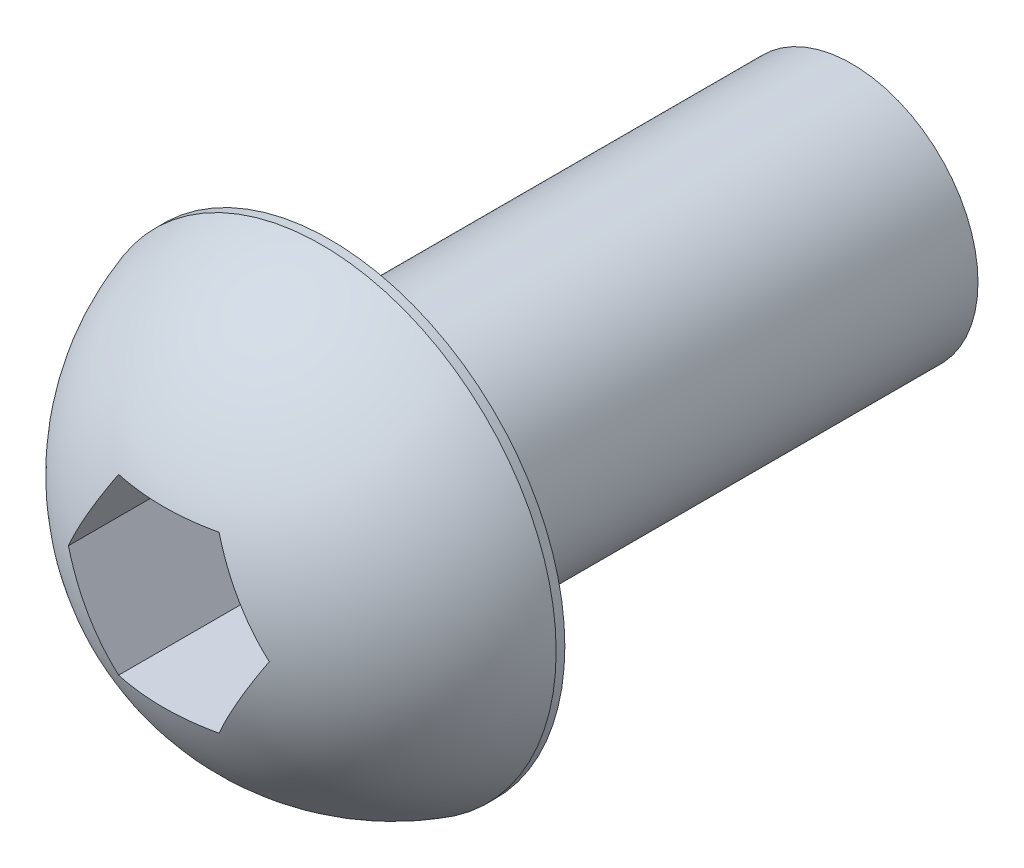
SolidWorks part; units mm, degrees
ref_plane "Front" through (0, 0, 0) normal (0, 0, 1) x (1, 0, 0)
ref_plane "Top" through (0, 0, 0) normal (0, 1, 0) x (1, 0, 0)
ref_plane "Right" through (0, 0, 0) normal (1, 0, 0) x (0, 0, -1)
sketch "Sketch1" plane through (0, 0, 0) normal (0, 0, 1) x (1, 0, 0)
  circle A0 centre (0, 0) radius 1.45
  dimension "D1" = 2.9
extrude "Boss-Extrude1" add sketch "Sketch1" along normal blind 6
cosmetic thread "Cosmetic Thread1" parameters "D2"=1.993
sketch "Sketch2" plane through (0, 0, 6) normal (0, 0, 1) x (1, 0, 0)
  circle A0 centre (0, 0) radius 2.7
  dimension "D1" = 5.4
extrude "Boss-Extrude2" add sketch "Sketch2" along normal blind 0.1
dome "Dome1" faces to dome 1 distance 2 reverse direction no elliptical dome no face at (2.7, 0, 6.1) parameters "D1"=2
sketch "Sketch3" plane through (0, 0, 6) normal (0, 0, -1) x (-1, 0, 0)
  line L1 (-0.5774, 1) -> (-1.1547, 0)
  line L2 (-1.1547, 0) -> (-0.5774, -1)
  line L3 (-0.5774, -1) -> (0.5774, -1)
  line L4 (0.5774, -1) -> (1.1547, 0)
  line L5 (1.1547, 0) -> (0.5774, 1)
  line L6 (0.5774, 1) -> (-0.5774, 1)
  circle A0 centre (0, 0) radius 1 construction
  dimension "D1" = 2
extrude "Cut-Extrude1" cut sketch "Sketch3" against normal through all
